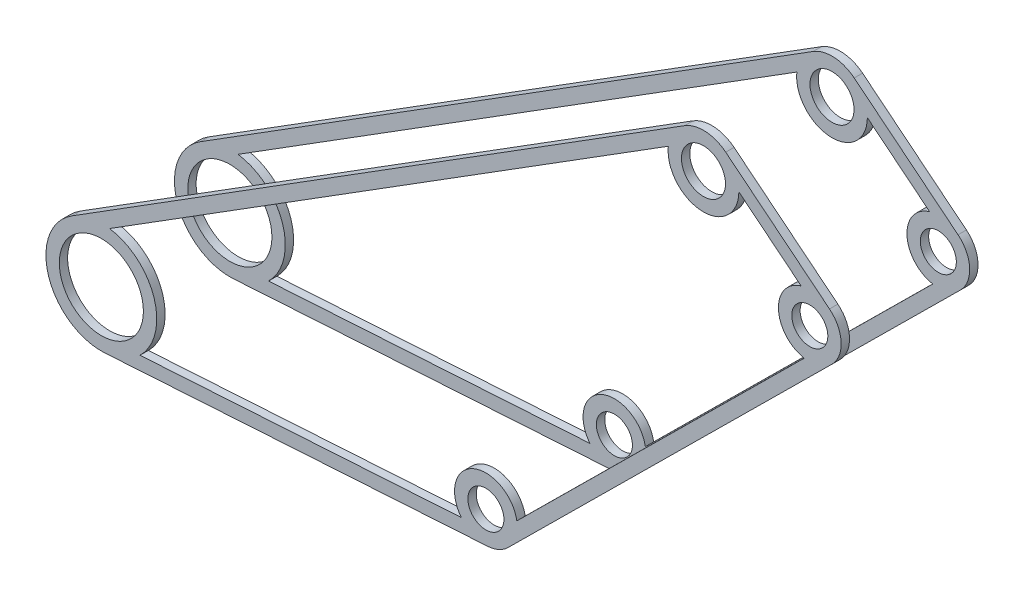
SolidWorks part; units mm, degrees
ref_plane "Front Plane" through (0, 0, 0) normal (0, 0, 1) x (1, 0, 0)
ref_plane "Top Plane" through (0, 0, 0) normal (0, 1, 0) x (1, 0, 0)
ref_plane "Right Plane" through (0, 0, 0) normal (1, 0, 0) x (0, 0, -1)
sketch "Sketch1" plane through (0, 0, 0) normal (0, 0, 1) x (1, 0, 0)
  line L0 (0, 0) -> (73.152, 0) construction
  line L1 (73.152, 0) -> (114.5399, 76.3747) construction
  line L2 (114.5399, 76.3747) -> (0, 0) construction
  line L3 (-5.6029, 8.9286) -> (110.9621, 82.0761)
  line L4 (120.4295, 73.1159) -> (78.3748, -2.8898)
  line L5 (73.5251, -5.9573) -> (0.6588, -10.5204)
  line L6 (-4.2528, 6.7771) -> (112.3122, 79.9246)
  line L7 (0.5001, -7.9854) -> (73.3663, -3.4223)
  line L8 (76.1523, -1.6601) -> (118.207, 74.3457)
  line L9 (114.5399, 76.3747) -> (134.7659, 61.0102) construction
  line L10 (138.9658, 56.7687) -> (77.3519, -4.2414)
  line L11 (75.5647, -2.4366) -> (137.1786, 58.5736)
  line L12 (138.5175, 65.6529) -> (118.7704, 81.61)
  line L13 (117.174, 79.6344) -> (136.9211, 63.6773)
  circle A0 centre (0, 0) radius 8.001
  circle A1 centre (73.152, 0) radius 3.429
  circle A2 centre (114.5399, 76.3747) radius 4.191
  circle A3 centre (0, 0) radius 10.541
  circle A4 centre (73.152, 0) radius 5.969
  circle A5 centre (114.5399, 76.3747) radius 6.731
  circle A6 centre (134.7659, 61.0102) radius 3.429
  circle A7 centre (134.7659, 61.0102) radius 5.969
  dimension "D1" = 8.382
  dimension "D2" = 6.858
  dimension "D3" = 16.002
  dimension "D10" = 6.858
  dimension "D4" = 73.152
  dimension "D5" = 86.868
  dimension "D6" = 2.54
  dimension "D7" = 2.54
  dimension "D8" = 2.54
  dimension "D9" = 137.668
  dimension "D11" = 2.54
  dimension "D12" = 25.4
  dimension "D13" = 109.083
extrude "Boss-Extrude1" add sketch "Sketch1" along normal blind 1.5875 from offset 11.43 contours A5 L3 A3 L6 | A5 L6 A2 L13 | L6 A5 L8 A2 | L8 A5 L13 A2 | A7 L12 A5 L13 | L13 A7 L11 A6 | A7 L13 A6 L11 | A7 L11 L4 A4 L10 | A4 L4 L11 | L7 A4 L11 A1 | L8 A4 L7 A1 | L11 A4 L8 A1 | A4 L7 A3 L5 | L6 A3 L7 A0 | L7 A3 L6 A0 | A5 | A2 region at (-2.0989, 10.0476, 0) region at (53.7785, 44.7109, 0) region at (114.932, 82.9436, 0) region at (37.6389, -6.9621, 0) region at (7.8072, 6.7258, 0) region at (127.9927, 72.6417, 0) region at (111.5933, 73.2613, 0) region at (74.7514, -3.567, 0) region at (140.0244, 63.5217, 0) region at (118.9467, 73.9414, 0) region at (107.8881, 27.7351, 0) region at (70.041, 4.9185, 0) region at (134.931, 65.1013, 0) region at (77.836, 0.5261, 0) region at (80.1305, 1.1443, 0)
extrude "Boss-Extrude2" add sketch "Sketch1<4>" against normal blind 1.5875 from offset 11.43 separate body contours A7 L13 A6 L11 | A7 L12 A5 L13 | A7 L11 L4 A4 L10 | L13 A7 L11 A6 | L7 A4 L11 A1 | A4 L4 L11 | L11 A4 L8 A1 | L8 A4 L7 A1 | A4 L7 A3 L5 | L6 A3 L7 A0 | L7 A3 L6 A0 | A5 L3 A3 L6 | A5 L6 A2 L13 | L6 A5 L8 A2 | L8 A5 L13 A2 region at (-2.0989, 10.0476, 0) region at (53.7785, 44.7109, 0) region at (114.932, 82.9436, 0) region at (37.6389, -6.9621, 0) region at (7.8072, 6.7258, 0) region at (127.9927, 72.6417, 0) region at (111.5933, 73.2613, 0) region at (74.7514, -3.567, 0) region at (140.0244, 63.5217, 0) region at (118.9467, 73.9414, 0) region at (107.8881, 27.7351, 0) region at (70.041, 4.9185, 0) region at (134.931, 65.1013, 0) region at (77.836, 0.5261, 0) region at (80.1305, 1.1443, 0) offset against normal yes
sketch "Sketch1<4>" plane through (0, 0, 0) normal (0, 0, 1) x (1, 0, 0) same geometry as "Sketch1"
equation "\"D19@Boss-Extrude2\"=.45"
equation "\"Perpendicular ARB Rocker Length\"= 1.0in"
equation "\"D12@Sketch1\"=\"Perpendicular ARB Rocker Length\""
